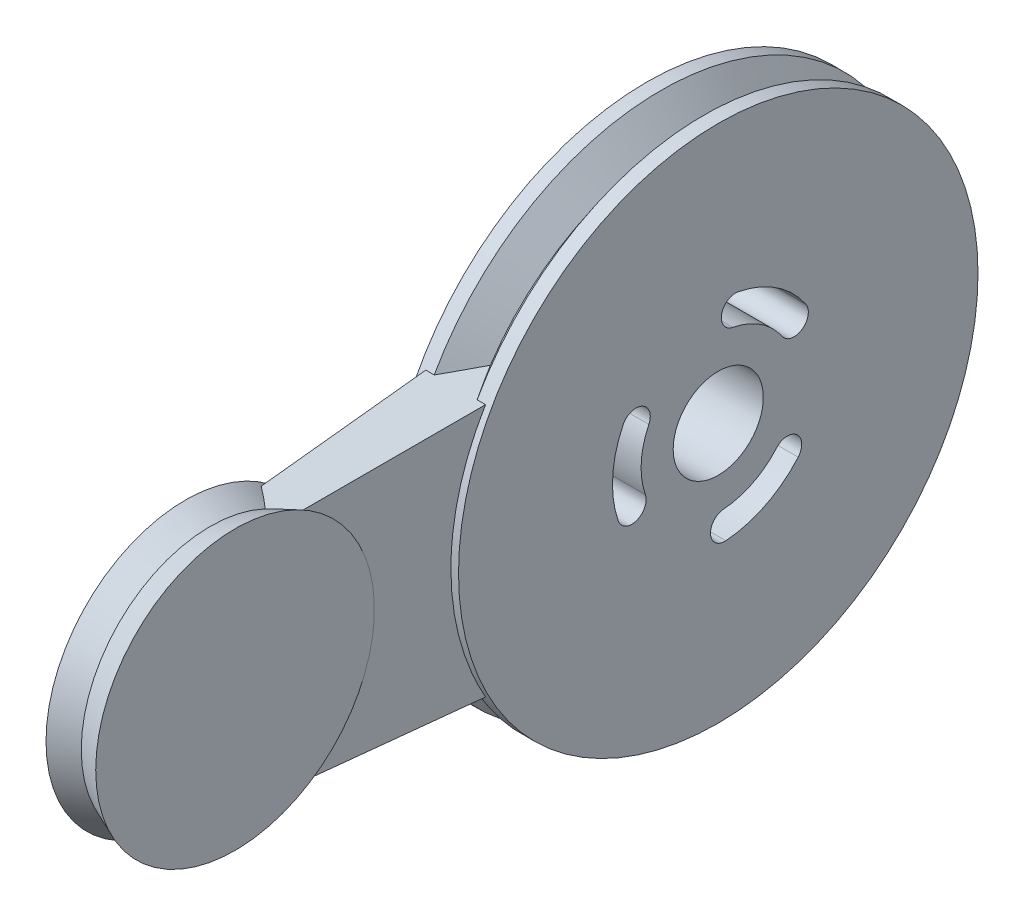
SolidWorks part; units mm, degrees
ref_plane "Front Plane" through (0, 0, 0) normal (0, 0, 1) x (1, 0, 0)
ref_plane "Top Plane" through (0, 0, 0) normal (0, 1, 0) x (1, 0, 0)
ref_plane "Right Plane" through (0, 0, 0) normal (1, 0, 0) x (0, 0, -1)
sketch "Sketch1" plane through (0, 0, 0) normal (0, 0, 1) x (1, 0, 0)
  line L0 (0, 0) -> (16.5774, 0) construction
  line L1 (1.27, 23.05) -> (3.175, 20.51)
  line L2 (0, 4) -> (6.35, 4)
  line L3 (0, 4) -> (0, 23.05)
  line L4 (0, 23.05) -> (1.27, 23.05)
  line L5 (6.35, 4) -> (6.35, 23.05)
  line L6 (3.175, 20.51) -> (5.08, 23.05)
  line L7 (3.175, 20.51) -> (3.175, 4) construction
  line L8 (5.08, 23.05) -> (6.35, 23.05)
  dimension "D1" = 8
  dimension "D2" = 19.05
  dimension "D3" = 6.35
  dimension "D4" = 1.27
  dimension "D5" = 2.54
revolve "Revolve1" add sketch "Sketch1" angle 360 about L0
sketch "Sketch2" plane through (0, 0, 0) normal (-1, 0, 0) x (0, 0, 1)
  arc A0 (-5.1749, -4.4843) -> (-7.0945, -6.1476) centre (-6.1347, -5.3159) ccw construction
  arc A1 (-5.1749, -4.4843) -> (-0.4884, -6.8301) centre (0, 0) ccw construction
  arc A2 (-0.6695, -9.3636) -> (-0.4884, -6.8301) centre (-0.5789, -8.0968) ccw construction
  arc A3 (-7.0945, -6.1476) -> (-0.6695, -9.3636) centre (0, 0) ccw construction
  arc A4 (-5.1749, -4.4843) -> (-7.0945, -6.1476) centre (-6.1347, -5.3159) ccw
  arc A5 (-5.1749, -4.4843) -> (-0.4884, -6.8301) centre (0, 0) ccw
  arc A6 (-0.6695, -9.3636) -> (-0.4884, -6.8301) centre (-0.5789, -8.0968) ccw
  arc A7 (-7.0945, -6.1476) -> (-0.6695, -9.3636) centre (0, 0) ccw
  arc A8 (-1.296, 6.7237) -> (-1.7768, 9.2178) centre (-1.5364, 7.9708) ccw
  arc A9 (-1.7768, 9.2178) -> (-7.7743, 5.2616) centre (0, 0) ccw
  arc A10 (-7.7743, 5.2616) -> (-5.6708, 3.838) centre (-6.7226, 4.5498) ccw
  arc A11 (-1.296, 6.7237) -> (-5.6708, 3.838) centre (0, 0) ccw
  arc A12 (6.4709, -2.2395) -> (8.8712, -3.0702) centre (7.6711, -2.6548) ccw
  arc A13 (8.8712, -3.0702) -> (8.4439, 4.102) centre (0, 0) ccw
  arc A14 (8.4439, 4.102) -> (6.1592, 2.9921) centre (7.3015, 3.547) ccw
  arc A15 (6.4709, -2.2395) -> (6.1592, 2.9921) centre (0, 0) ccw
  point P21 (0, 0)
  dimension "D1" = 3
extrude "Cut-Extrude1" cut sketch "Sketch2" against normal through all both and the other way through all
ref_plane "Plane1" through (0, 0, 10.16) normal (0, 0, 1) x (1, 0, 0)
sketch "Sketch4" plane through (0, 0, 10.16) normal (0, 0, 1) x (1, 0, 0)
  line L0 (0, 11.7571) -> (6.35, 11.7571)
  line L1 (0, 23.05) -> (0, -23.05) construction
  line L2 (6.35, -23.05) -> (6.35, 23.05) construction
  line L3 (6.35, 11.7571) -> (6.35, -11.7571)
  line L4 (6.35, -11.7571) -> (0, -11.7571)
  line L5 (0, -11.7571) -> (0, 11.7571)
  line L6 (0, 0) -> (6.35, 0) construction
extrude "Boss-Extrude1" add sketch "Sketch4" along normal blind 31.75 draft 3
sketch "Sketch7" plane through (0, 0, 41.91) normal (0, 0, 1) x (1, 0, 0)
  line L0 (0, 0) -> (6.5526, 0) construction
  line L1 (0.9697, 0) -> (0.9697, 12.3665)
  line L3 (5.3803, 12.3665) -> (5.3803, 0)
  line L4 (5.3803, 0) -> (0.9697, 0)
  line L5 (3.175, 14.1418) -> (3.175, -10.586) construction
  line L6 (3.175, 20.51) -> (3.175, -20.51) construction
  line L7 (0.9697, 12.3665) -> (3.175, 11.4433)
  line L8 (3.175, 11.4433) -> (5.3803, 12.3665)
  point P11 (0, 0)
  point P12 (0, 0)
  point P14 (5.327, 12.305)
  point P15 (5.6753, 13.7653)
  point P16 (3.175, 12.5341)
  point P17 (0.9351, 12.8627)
  point P18 (3.175, 11.4433)
  point P19 (0.9697, 12.3665)
revolve "Revolve2" add sketch "Sketch7" angle 360 about L0
